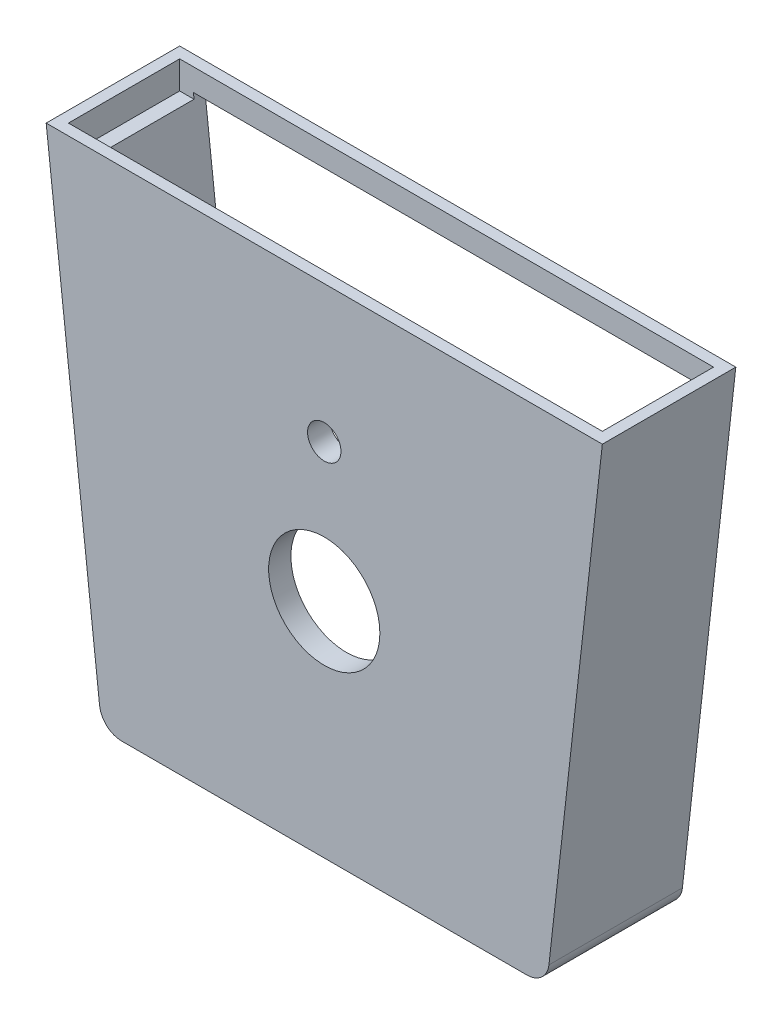
SolidWorks part; units mm, degrees
ref_plane "Front Plane" through (0, 0, 0) normal (0, 0, 1) x (1, 0, 0)
ref_plane "Top Plane" through (0, 0, 0) normal (0, 1, 0) x (1, 0, 0)
ref_plane "Right Plane" through (0, 0, 0) normal (1, 0, 0) x (0, 0, -1)
sketch "Sketch1" plane through (0, 0, 0) normal (0, 0, 1) x (1, 0, 0)
  line L0 (0, 56.7961) -> (0, -56.7961) construction
  line L1 (63.5, 56.7961) -> (-63.5, 56.7961)
  line L2 (-63.5, 56.7961) -> (-51.3049, -52.2806)
  line L3 (-46.2563, -56.7961) -> (46.2563, -56.7961)
  line L4 (63.5, 56.7961) -> (51.3049, -52.2806)
  arc A0 (-51.3049, -52.2806) -> (-46.2563, -56.7961) centre (-46.2563, -51.7161) ccw
  arc A1 (51.3049, -52.2806) -> (46.2563, -56.7961) centre (46.2563, -51.7161) cw
  circle A2 centre (0, 25.5165) radius 3.81
  circle A3 centre (0, -5.9961) radius 12.7
  point P10 (-50.8, -56.7961)
  dimension "D4" = 5.08
  dimension "D6" = 7.62
  dimension "D7" = 25.4
  dimension "D8" = 31.2797
  dimension "D9" = 50.8
  dimension "D1" = 50.8
  dimension "D2" = 63.5
  dimension "D3" = 56.7961
  dimension "D5" = 109.0767
extrude "Boss-Extrude1" add sketch "Sketch1" against normal blind 5.08
sketch "Sketch2" plane through (0, 0, -5.08) normal (0, 0, 1) x (1, 0, 0)
  line L0 (0, 56.7961) -> (0, -56.7961) construction
  line L1 (63.5, 56.7961) -> (-63.5, 56.7961)
  line L2 (-63.5, 56.7961) -> (-51.3049, -52.2806)
  line L3 (-46.2563, -56.7961) -> (46.2563, -56.7961)
  line L4 (63.5, 56.7961) -> (51.3049, -52.2806)
  line L5 (-46.2563, -56.7961) -> (46.2563, -56.7961) construction
  line L6 (-57.8204, 51.7161) -> (57.8204, 51.7161)
  line L7 (57.8204, 51.7161) -> (46.7612, -47.2006)
  line L8 (41.7126, -51.7161) -> (-41.7126, -51.7161)
  line L9 (-57.8204, 51.7161) -> (-46.7612, -47.2006)
  arc A0 (-51.3049, -52.2806) -> (-46.2563, -56.7961) centre (-46.2563, -51.7161) ccw
  arc A1 (51.3049, -52.2806) -> (46.2563, -56.7961) centre (46.2563, -51.7161) cw
  circle A2 centre (0, 26.1693) radius 3.81
  circle A3 centre (0, -32.9791) radius 12.7
  arc A4 (46.7612, -47.2006) -> (41.7126, -51.7161) centre (41.7126, -46.6361) cw
  arc A5 (-46.7612, -47.2006) -> (-41.7126, -51.7161) centre (-41.7126, -46.6361) ccw
  point P10 (-50.8, -56.7961)
  point P27 (0, -51.7161)
  point P28 (0, 51.7161)
  arc M12 (51.3049, -52.2806) -> (46.2563, -56.7961) centre (46.2563, -51.7161) cw
  line M13 (46.2563, -56.7961) -> (-46.2563, -56.7961)
  arc M14 (-46.2563, -56.7961) -> (-51.3049, -52.2806) centre (-46.2563, -51.7161) cw
  line M15 (-51.3049, -52.2806) -> (-63.5, 56.7961)
  line M16 (-63.5, 56.7961) -> (63.5, 56.7961)
  line M17 (63.5, 56.7961) -> (51.3049, -52.2806)
  dimension "D4" = 5.08
  dimension "D6" = 7.62
  dimension "D7" = 25.4
  dimension "D8" = 30.6268
  dimension "D9" = 23.8171
  dimension "D11" = 5.08
  dimension "D1" = 50.8
  dimension "D2" = 63.5
  dimension "D3" = 5.08
  dimension "D5" = 109.0767
  dimension "D10" = 0
extrude "Boss-Extrude2" add sketch "Sketch2" against normal blind 25.4 contours L0 L1 L8 A4 L7 L6 M17 M12 M13 | L0 L6 L9 A5 L8 L3 M16 M14 M15 region at (31.75, 55.4948, -5.08) region at (-1.3014, 54.2561, -5.08)
sketch "Sketch3" plane through (0, 56.7961, 0) normal (0, 1, 0) x (1, 0, 0)
  line L0 (60.96, 2.54) -> (60.96, 27.94)
  line L1 (60.96, 2.54) -> (-60.96, 2.54)
  line L2 (60.96, 27.94) -> (-60.96, 27.94)
  line L3 (-60.96, 2.54) -> (-60.96, 27.94)
  line L4 (-63.5, 30.48) -> (63.5, 30.48) construction
  line L5 (63.5, 30.48) -> (63.5, 0) construction
  line L6 (63.5, 0) -> (-63.5, 0) construction
  line L8 (-63.5, 30.48) -> (-63.5, 0) construction
  dimension "D1" = 2.54
  dimension "D2" = 2.54
  dimension "D3" = 2.54
  dimension "D4" = 2.54
extrude "Cut-Extrude2" cut sketch "Sketch3" against normal blind 6.35
sketch "Sketch4" plane through (0, 0, -30.48) normal (0, 0, -1) x (-1, 0, 0)
  line L0 (0, 51.7161) -> (0, -51.7161) construction
  line L1 (57.8204, 51.7161) -> (-57.8204, 51.7161) construction
  line L2 (-41.7126, -51.7161) -> (41.7126, -51.7161) construction
  line L3 (-52.9958, 8.564) -> (-33.9458, 8.564)
  line L4 (-57.6784, 50.4461) -> (-46.7612, -47.2006) construction
  line L5 (-33.9458, 8.564) -> (-33.9458, -4.136)
  line L6 (-33.9458, -4.136) -> (-51.5759, -4.136)
  line L7 (-57.8204, 51.7161) -> (-46.7612, -47.2006) construction
  line L8 (33.9458, -4.136) -> (51.5759, -4.136)
  line L9 (33.9458, 8.564) -> (33.9458, -4.136)
  line L10 (52.9958, 8.564) -> (33.9458, 8.564)
  line L11 (-51.5759, -4.136) -> (-52.9958, 8.564)
  line L12 (52.9958, 8.564) -> (51.5759, -4.136)
  dimension "D1" = 19.05
  dimension "D2" = 12.7
  dimension "D3" = 33.9458
extrude "Boss-Extrude3" add sketch "Sketch4" against normal blind 2.54
sketch "Sketch5" plane through (0, 0, -30.48) normal (0, 0, -1) x (-1, 0, 0)
  line L0 (-43.4708, 8.564) -> (-42.7609, -4.136) construction
  line L1 (-33.9458, 8.564) -> (-52.9958, 8.564) construction
  line L2 (-51.5759, -4.136) -> (-33.9458, -4.136) construction
  line L3 (0, 51.7161) -> (0, -51.7161) construction
  line L4 (57.8204, 51.7161) -> (-57.8204, 51.7161) construction
  line L5 (-41.7126, -51.7161) -> (41.7126, -51.7161) construction
  circle A0 centre (-43.1159, 2.214) radius 1.905
  circle A1 centre (43.1159, 2.214) radius 1.905
  dimension "D1" = 3.81
extrude "Cut-Extrude3" cut sketch "Sketch5" against normal blind 2.54
